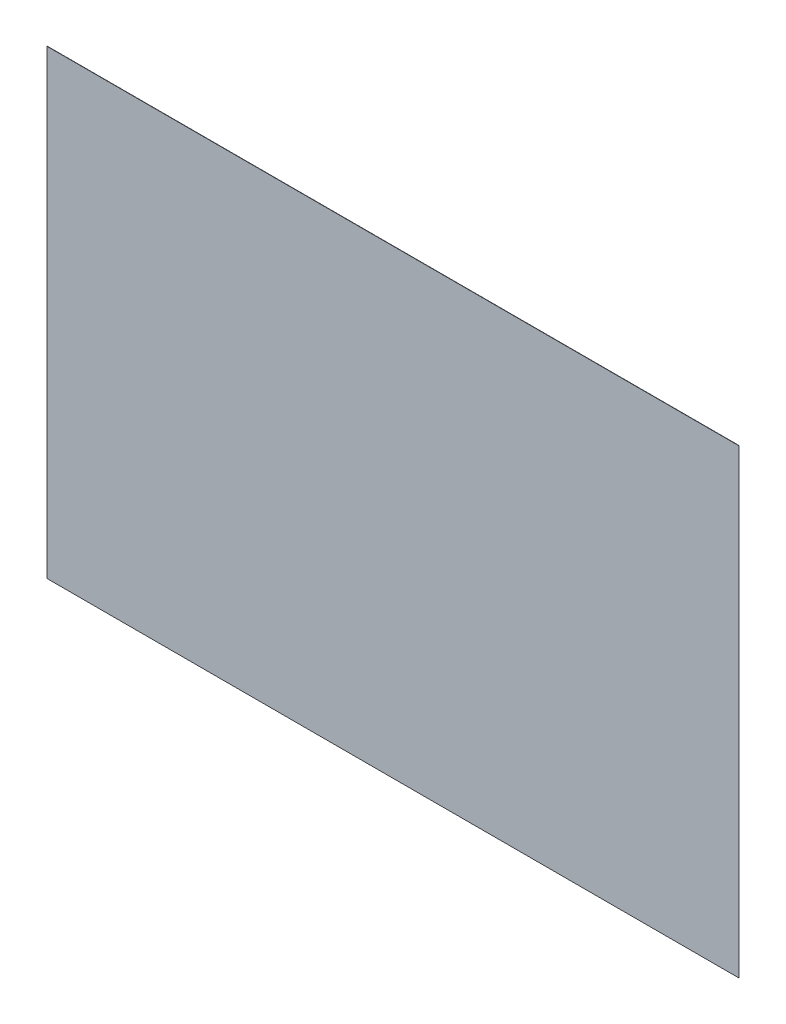
SolidWorks part; units mm, degrees
ref_plane "Front Plane" through (0, 0, 0) normal (0, 0, 1) x (1, 0, 0)
ref_plane "Top Plane" through (0, 0, 0) normal (0, 1, 0) x (1, 0, 0)
ref_plane "Right Plane" through (0, 0, 0) normal (1, 0, 0) x (0, 0, -1)
sketch "Sketch1" plane through (0, 0, 0) normal (0, 0, 1) x (1, 0, 0)
  line L1 (0, 0) -> (2440, 0)
  line L2 (0, 0) -> (0, 1625)
  line L3 (0, 1625) -> (2440, 1625)
  line L4 (2440, 0) -> (2440, 1625)
  dimension "D1" = 2440
  dimension "D2" = 1625
extrude "Boss-Extrude1" add sketch "Sketch1" along normal blind 1
